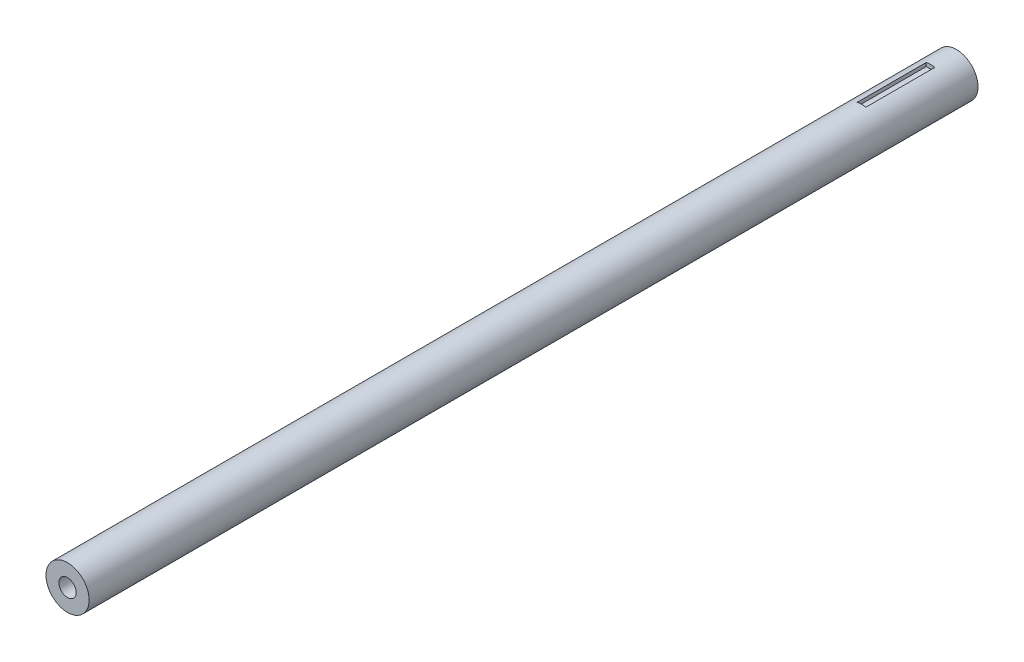
SolidWorks part; units mm, degrees
ref_plane "Front" through (0, 0, 0) normal (0, 0, 1) x (1, 0, 0)
ref_plane "Top" through (0, 0, 0) normal (0, 1, 0) x (1, 0, 0)
ref_plane "Right" through (0, 0, 0) normal (1, 0, 0) x (0, 0, -1)
sketch "Sketch1" plane through (0, 0, 0) normal (0, 0, 1) x (1, 0, 0)
  circle A0 centre (0, 0) radius 7.9375
  dimension "D1" = 15.875
extrude "Extrude1" add sketch "Sketch1" along normal blind 136.525 and the other way blind 190.5
ref_axis "Axis1" through (0, 0, 136.525) along (0, 0, -1)
sketch "Sketch2" plane through (0, 0, 136.525) normal (0, 0, 1) x (1, 0, 0)
  circle A0 centre (0, 0) radius 3.175
  dimension "D1" = 6.35
extrude "Cut-Extrude1" cut sketch "Sketch2" against normal blind 25.4
sketch "Sketch3" plane through (0, 0, 0) normal (1, 0, 0) x (0, 0, -1)
  line L0 (190.5, 7.9375) -> (-136.525, 7.9375) construction
  line L1 (190.5, -7.9375) -> (190.5, 7.9375) construction
  line L3 (155.575, 9.6139) -> (180.975, 9.6139)
  line L4 (155.575, 9.6139) -> (155.575, 6.4389)
  line L5 (155.575, 6.4389) -> (180.975, 6.4389)
  line L6 (180.975, 9.6139) -> (180.975, 6.4389)
  point P2 (180.975, 7.9375)
  dimension "D1" = 3.175
  dimension "D2" = 9.525
  dimension "D3" = 1.4986
  dimension "D4" = 25.4
extrude "Cut-Extrude2" cut sketch "Sketch3" against normal mid plane 3.175
